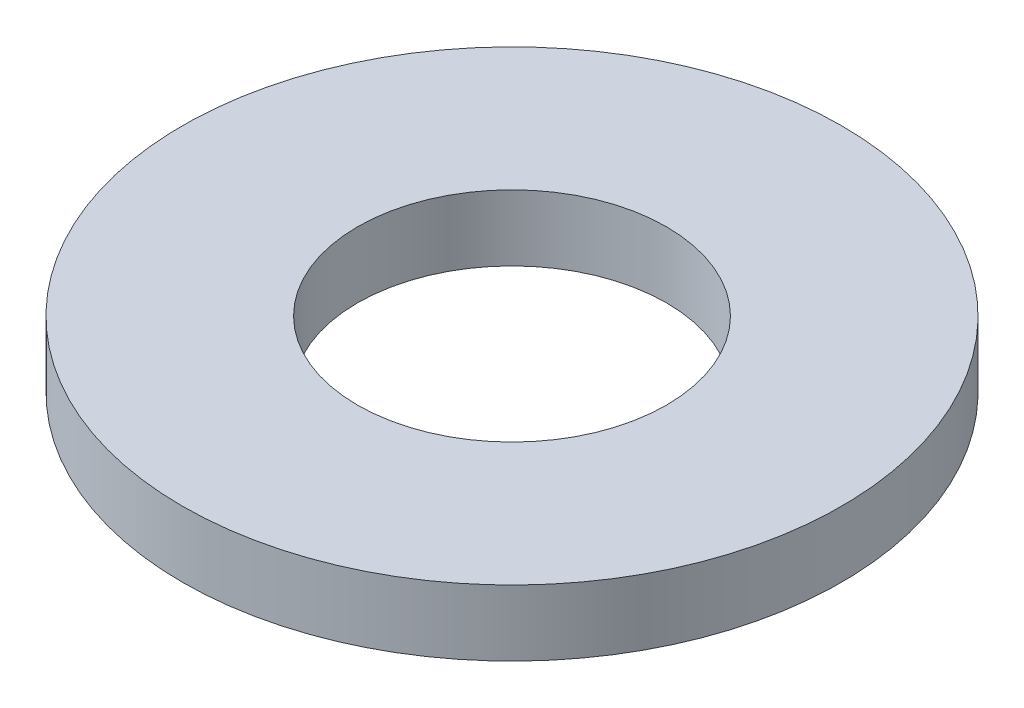
SolidWorks part; units mm, degrees
ref_plane "Front Plane" through (0, 0, 0) normal (0, 0, 1) x (1, 0, 0)
ref_plane "Top Plane" through (0, 0, 0) normal (0, 1, 0) x (1, 0, 0)
ref_plane "Right Plane" through (0, 0, 0) normal (1, 0, 0) x (0, 0, -1)
sketch "Sketch1" plane through (0, 0, 0) normal (0, 1, 0) x (1, 0, 0)
  circle A0 centre (0, 0) radius 80
  dimension "FLANGE_OD" = 160
extrude "Boss-Extrude1" add sketch "Sketch1" along normal blind 16
sketch "Sketch2" plane through (0, 0, 0) normal (0, 1, 0) x (1, 0, 0)
  circle A0 centre (0, 0) radius 37.5
  dimension "BORE_D" = 75
extrude "Cut-Extrude1" cut sketch "Sketch2" along normal through all
sketch "Sketch3" plane through (0, 16, 0) normal (0, 1, 0) x (1, 0, 0)
  circle A0 centre (0, 0) radius 24.3176 construction
  circle A1 centre (-24.3176, 0) radius 3.6706
  dimension "BOLT_D" = 7.3412
  dimension "BOLT_PCD" = 48.6351
extrude "Cut-Extrude2" cut sketch "Sketch3" against normal blind 12.342 rebuild error yes
pattern_circular "CirPattern1" count 4 over 360 rebuild error yes
